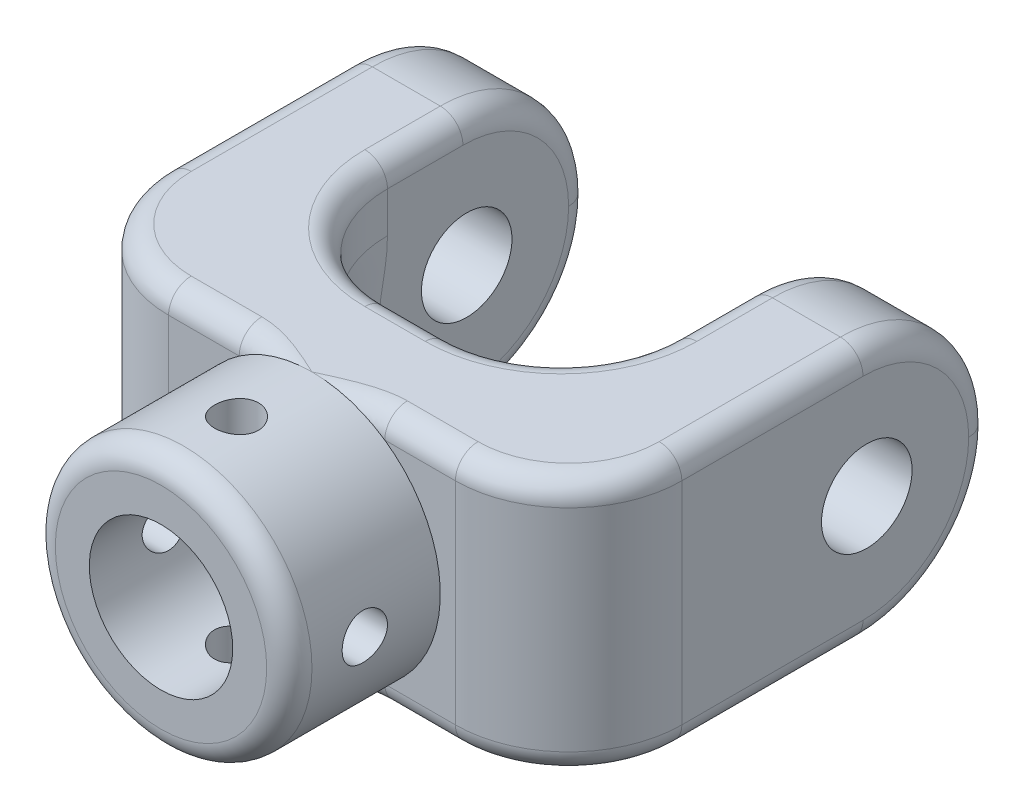
SolidWorks part; units mm, degrees
ref_plane "Front Plane" through (0, 0, 0) normal (0, 0, 1) x (1, 0, 0)
ref_plane "Top Plane" through (0, 0, 0) normal (0, 1, 0) x (1, 0, 0)
ref_plane "Right Plane" through (0, 0, 0) normal (1, 0, 0) x (0, 0, -1)
sketch "Sketch1" plane through (0, 0, 0) normal (0, 1, 0) x (1, 0, 0)
  line L0 (-34, 0) -> (34, 0)
  line L1 (34, 0) -> (34, 56)
  line L2 (34, 56) -> (19, 56)
  line L3 (19, 56) -> (19, 14)
  line L4 (19, 14) -> (-19, 14)
  line L5 (0, 14) -> (0, 0)
  line L6 (-19, 56) -> (-19, 14)
  line L7 (-34, 56) -> (-19, 56)
  line L8 (-34, 0) -> (-34, 56)
  dimension "D3" = 15
  dimension "D4" = 14
  dimension "D1" = 34
  dimension "D2" = 56
extrude "Boss-Extrude3" add sketch "Sketch1" along normal blind 34 contours L8 L0 L5 L4 L6 L7 | L4 L5 L0 L1 L2 L3 region at (-22.4114, 0, -22.9494) region at (22.4114, 0, -22.9494)
fillet "Fillet7" radius 17 4 edges at (-26.5, 0, -56) (-26.5, 34, -56) (26.5, 34, -56) (26.5, 0, -56)
sketch "Sketch5" plane through (34, 0, 0) normal (1, 0, 0) x (0, 0, -1)
  line L0 (0, 17) -> (56, 17) construction
  line L3 (39, 34) -> (0, 34)
  line L4 (0, 34) -> (0, 0)
  line L5 (0, 0) -> (39, 0)
  line L6 (39, 34) -> (0, 34)
  line L7 (0, 34) -> (0, 0)
  line L8 (0, 0) -> (39, 0)
  circle A1 centre (39.5, 17) radius 6
  arc A2 (39, 0) -> (56, 17) centre (39, 17) ccw
  arc A3 (56, 17) -> (39, 34) centre (39, 17) ccw
  arc A4 (39, 0) -> (56, 17) centre (39, 17) ccw
  arc A5 (56, 17) -> (39, 34) centre (39, 17) ccw
  dimension "D2" = 12
  dimension "D3" = 16.5
  dimension "D1" = 0
extrude "Cut-Extrude2" cut sketch "Sketch5" against normal through all both and the other way through all contours A1
sketch "Sketch6" plane through (0, 0, 0) normal (0, 0, 1) x (1, 0, 0)
  line L0 (34, 17) -> (-34, 17) construction
  line L1 (-34, 17) -> (0, 34) construction
  line L2 (0, 34) -> (0, 0) construction
  line L4 (-34, 0) -> (34, 0)
  line L5 (34, 0) -> (34, 34)
  line L6 (34, 34) -> (-34, 34)
  line L7 (-34, 34) -> (-34, 0)
  line L8 (-34, 0) -> (34, 0)
  line L9 (34, 0) -> (34, 34)
  line L10 (34, 34) -> (-34, 34)
  line L11 (-34, 34) -> (-34, 0)
  circle A0 centre (0, 17) radius 17
  circle A1 centre (0, 17) radius 9.5
  dimension "D2" = 34
  dimension "D3" = 19
  dimension "D1" = 0
extrude "Boss-Extrude4" add sketch "Sketch6" along normal blind 20 contours A0 A1 region at (-16.5192, 17, 0)
sketch "Sketch8" plane through (0, 0, 0) normal (0, 0, 1) x (1, 0, 0)
  circle A0 centre (0, 17) radius 9.5 construction
  circle A1 centre (0, 17) radius 9.5
extrude "Cut-Extrude3" cut sketch "Sketch8" against normal through all both and the other way through all
sketch "Sketch9" plane through (0, 0, 0) normal (1, 0, 0) x (0, 0, -1)
  line L0 (0, 34) -> (0, 0) construction
  line L1 (-20, 0) -> (0, 0) construction
  line L2 (-20, 34) -> (-20, 0) construction
  line L3 (0, 34) -> (-20, 34) construction
  line L4 (0, 34) -> (0, 0)
  line L5 (-20, 0) -> (0, 0)
  line L6 (-20, 34) -> (-20, 0)
  line L7 (0, 34) -> (-20, 34)
  line L8 (0, 17) -> (-20, 17) construction
  circle A0 centre (-10, 17) radius 3
  point P6 (0, 0)
  dimension "D1" = 6
  dimension "D2" = 10
extrude "Cut-Extrude5" cut sketch "Sketch9" against normal through all both and the other way through all contours A0
sketch "Sketch10" plane through (0, 0, 0) normal (0, 1, 0) x (1, 0, 0)
  line L0 (-34, 0) -> (0, 0) construction
  line L1 (0, 0) -> (34, 0) construction
  line L2 (17, -7) -> (17, 0) construction
  line L3 (-34, 0) -> (0, 0)
  line L4 (0, 0) -> (34, 0)
  line L5 (17, -7) -> (17, 0)
  line L6 (-17, 0) -> (-17, -7) construction
  line L7 (-17, -13) -> (-17, -20) construction
  line L8 (-17, -20) -> (17, -20) construction
  line L9 (17, -20) -> (17, -13) construction
  line L10 (-17, 0) -> (-17, -7)
  line L11 (-17, -13) -> (-17, -20)
  line L12 (-17, -20) -> (17, -20)
  line L13 (17, -20) -> (17, -13)
  circle A0 centre (0, -10) radius 2.91
  spline S0 degree 2 poles (17, -13) (16.4706, -10) (17, -7) knots 0 0 0 1 1 1 weights 0.014 0.017 0.02 construction
  spline S1 degree 2 poles (-17, -7) (-16.4706, -10) (-17, -13) knots 0 0 0 1 1 1 weights 0.014 0.017 0.02 construction
  spline S2 degree 2 poles (17, -13) (16.4706, -10) (17, -7) knots 0 0 0 1 1 1 weights 0.014 0.017 0.02
  spline S3 degree 2 poles (-17, -7) (-16.4706, -10) (-17, -13) knots 0 0 0 1 1 1 weights 0.014 0.017 0.02
  point P15 (0, 0)
  dimension "D1" = 5.82
  dimension "D2" = 10
extrude "Cut-Extrude6" cut sketch "Sketch10" against normal through all both and the other way through all contours A0
fillet "Fillet8" radius 15 4 edges at (19, 17, -14) (-34, 17, 0) (34, 17, 0) (-19, 17, -14)
fillet "Fillet9" radius 3 31 edges at (19, 29.0208, -51.0208) (19, 34, -34) (14.6066, 34, -18.3934) (0, 34, -14) (-14.6066, 34, -18.3934) (-19, 34, -34) (-19, 29.0208, -51.0208) (-19, 4.9792, -51.0208) (-19, 0, -34) (-14.6066, 0, -18.3934) (0, 0, -14) (14.6066, 0, -18.3934) (19, 0, -34) (-29.6066, 0, -4.3934) (-9.5, 0, 0) (9.5, 0, 0) (29.6066, 0, -4.3934) (34, 0, -27) (34, 4.9792, -51.0208) (34, 29.0208, -51.0208) (34, 34, -27) (29.6066, 34, -4.3934) (9.5, 34, 0) (-9.5, 34, 0) (-29.6066, 34, -4.3934) (-34, 34, -27) (-34, 29.0208, -51.0208) (-34, 4.9792, -51.0208) (17, 17, 20) (19, 4.9792, -51.0208) (-34, 0, -27)
